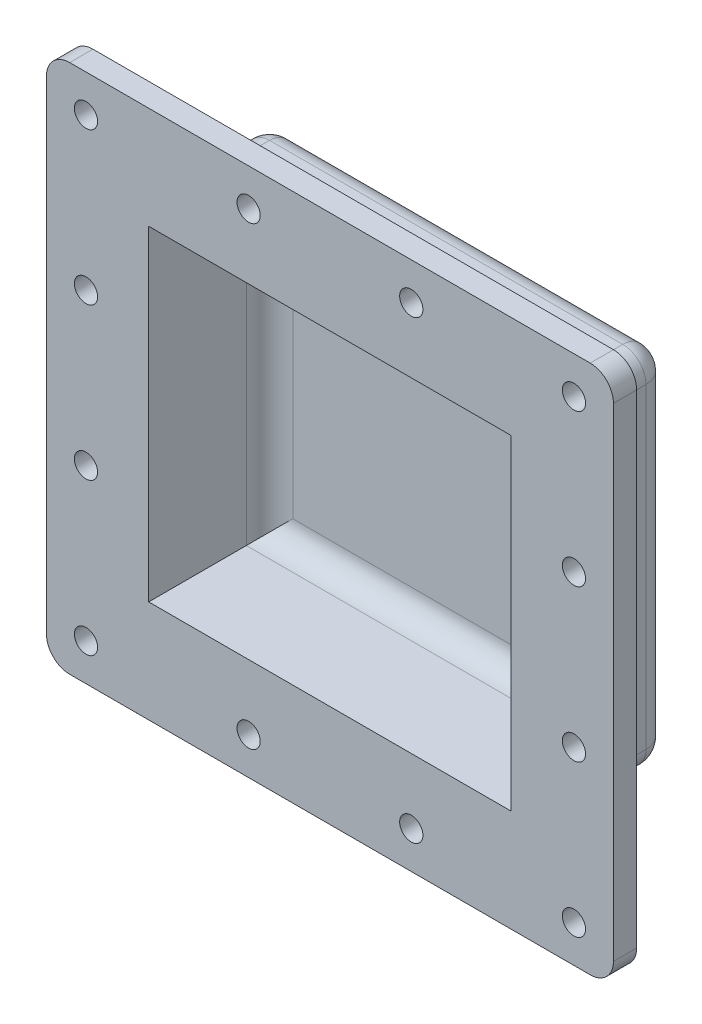
SolidWorks part; units mm, degrees
ref_plane "Front Plane" through (0, 0, 0) normal (0, 0, 1) x (1, 0, 0)
ref_plane "Top Plane" through (0, 0, 0) normal (0, 1, 0) x (1, 0, 0)
ref_plane "Right Plane" through (0, 0, 0) normal (1, 0, 0) x (0, 0, -1)
sketch "Sketch1" plane through (0, 0, 0) normal (0, 0, 1) x (1, 0, 0)
  line L1 (-21.5, 19.5) -> (21.5, 19.5)
  line L2 (-21.5, 19.5) -> (-21.5, -19.5)
  line L3 (-21.5, -19.5) -> (21.5, -19.5)
  line L4 (21.5, 19.5) -> (21.5, -19.5)
  line L5 (-21.5, 19.5) -> (21.5, -19.5) construction
  line L6 (-21.5, -19.5) -> (21.5, 19.5) construction
  point P0 (0, 0)
  dimension "D1" = 43
  dimension "D2" = 39
extrude "Boss-Extrude1" add sketch "Sketch1" along normal blind 12.5
shell "Shell1" thickness 2 removed face at (0, 0, 12.5)
sketch "Sketch2" plane through (0, 0, 12.5) normal (0, 0, 1) x (1, 0, 0)
  line L0 (-21.5, 19.5) -> (-21.5, -19.5) construction
  line L1 (-30.5, 28.5) -> (30.5, 28.5)
  line L2 (-30.5, 28.5) -> (-30.5, -28.5)
  line L3 (-30.5, -28.5) -> (30.5, -28.5)
  line L4 (30.5, 28.5) -> (30.5, -28.5)
  line L5 (-30.5, 28.5) -> (30.5, -28.5) construction
  line L6 (-30.5, -28.5) -> (30.5, 28.5) construction
  line L7 (-21.5, 19.5) -> (21.5, 19.5) construction
  line L8 (19.5, -17.5) -> (19.5, 17.5) construction
  line L9 (-19.5, -17.5) -> (19.5, -17.5)
  line L10 (-19.5, -17.5) -> (-19.5, 17.5)
  line L11 (-19.5, 17.5) -> (19.5, 17.5)
  line L12 (19.5, -17.5) -> (19.5, 17.5)
  line L13 (-19.5, -17.5) -> (19.5, 17.5) construction
  line L14 (-19.5, 17.5) -> (19.5, -17.5) construction
  line L15 (19.5, -17.5) -> (19.5, 17.5) construction
  point P0 (0, 0)
  point P10 (0, 0)
  dimension "D1" = 9
  dimension "D2" = 9
extrude "Boss-Extrude2" add sketch "Sketch2" along normal blind 2.5
fillet "Fillet1" radius 2.5 4 edges at (-30.5, -28.5, 13.75) (30.5, -28.5, 13.75) (30.5, 28.5, 13.75) (-30.5, 28.5, 13.75)
fillet "Fillet2" radius 2.5 12 edges at (0, -17.5, 2) (19.5, 0, 2) (-19.5, 0, 2) (0, 17.5, 2) (0, -19.5, 0) (21.5, 0, 0) (0, 19.5, 0) (-21.5, 0, 0) (21.5, -19.5, 6.25) (21.5, 19.5, 6.25) (-21.5, -19.5, 6.25) (-21.5, 19.5, 6.25)
sketch "Sketch3" plane through (0, 0, 2) normal (0, 0, 1) x (1, 0, 0)
  line L1 (-7.5, 14) -> (7.5, 14)
  line L2 (-7.5, 14) -> (-7.5, 6)
  line L3 (-7.5, 6) -> (7.5, 6)
  line L4 (7.5, 14) -> (7.5, 6)
  line L5 (-7.5, 14) -> (7.5, 6) construction
  line L6 (-7.5, 6) -> (7.5, 14) construction
  point P0 (0, 10)
  dimension "D1" = 8
  dimension "D2" = 15
  dimension "D3" = 10
extrude "Cut-Extrude1" cut sketch "Sketch3" against normal through all
sketch "Sketch4" plane through (0, 0, 15) normal (0, 0, 1) x (1, 0, 0)
  line L1 (-21.5, 19.5) -> (-21.5, -19.5) construction
  line L2 (-21.5, 19.5) -> (21.5, 19.5) construction
  line L3 (-26.25, 24.5) -> (26.25, 24.5) construction
  line L10 (-26.25, 24.5) -> (-26.25, -24.5) construction
  line L11 (-26.25, -24.5) -> (26.25, -24.5) construction
  line L18 (26.25, 24.5) -> (26.25, -24.5) construction
  line L19 (-26.25, 24.5) -> (26.25, -24.5) construction
  line L20 (-26.25, -24.5) -> (26.25, 24.5) construction
  circle A21 centre (-26.25, 24.5) radius 1.25
  circle A25 centre (-8.75, 24.5) radius 1.25
  circle A26 centre (8.75, 24.5) radius 1.25
  circle A27 centre (26.25, 24.5) radius 1.25
  circle A30 centre (26.25, 8.1667) radius 1.25
  circle A33 centre (26.25, -8.1667) radius 1.25
  circle A34 centre (-8.75, -24.5) radius 1.25
  circle A35 centre (8.75, -24.5) radius 1.25
  circle A36 centre (26.25, -24.5) radius 1.25
  circle A37 centre (-26.25, 8.1667) radius 1.25
  circle A38 centre (-26.25, -8.1667) radius 1.25
  circle A39 centre (-26.25, -24.5) radius 1.25
  circle A40 centre (-8.75, 8.1667) radius 1.25 [skipped]
  circle A41 centre (8.75, 8.1667) radius 1.25 [skipped]
  circle A42 centre (-8.75, -8.1667) radius 1.25 [skipped]
  circle A43 centre (8.75, -8.1667) radius 1.25 [skipped]
  point P0 (0, 0)
  dimension "D1" = 4.75
  dimension "D3" = 2.5
  dimension "D2" = 5
  dimension "D5" = 4
  dimension "D4" = 4
extrude "Cut-Extrude2" cut sketch "Sketch4" against normal up to surface (2.5 mm away) up to face at (0, 0, 12.5)
equation "\"case_width\"=43.00"
equation "\"D1@Sketch1\"=\"case_width\""
